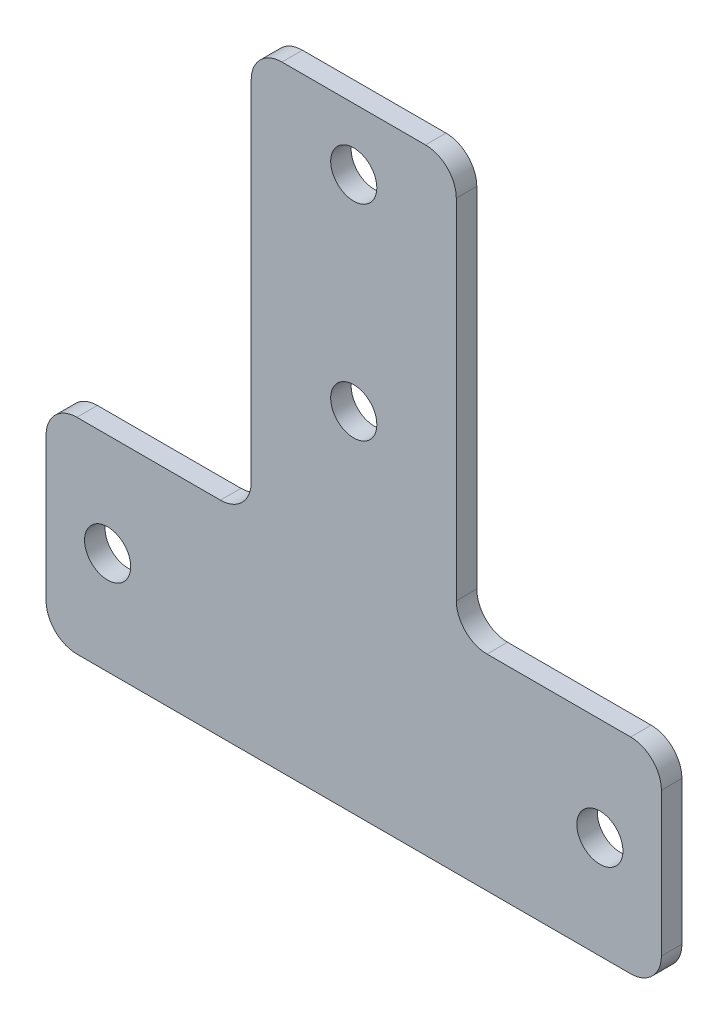
SolidWorks part; units mm, degrees
material "1023 碳钢板 (SS)"
ref_plane "前视基准面" through (0, 0, 0) normal (0, 0, 1) x (1, 0, 0)
ref_plane "上视基准面" through (0, 0, 0) normal (0, 1, 0) x (1, 0, 0)
ref_plane "右视基准面" through (0, 0, 0) normal (1, 0, 0) x (0, 0, -1)
sketch "草图1" plane through (0, 0, 0) normal (0, 0, 1) x (1, 0, 0)
  line L0 (0, 0) -> (37798.9194, 0) construction
  line L1 (0, 0) -> (0, 37798.9194) construction
  line L2 (-27, 0) -> (27, 0)
  line L3 (30, 3) -> (30, 17)
  line L4 (27, 20) -> (13, 20)
  line L5 (10, 23) -> (10, 32.5)
  line L6 (7, 60) -> (-7, 60)
  line L7 (-10, 57) -> (-10, 23)
  line L8 (-13, 20) -> (-27, 20)
  line L9 (-30, 17) -> (-30, 3)
  line L13 (10, 32.5) -> (10, 57)
  arc A0 (7, 60) -> (10, 57) centre (7, 57) cw
  arc A1 (13, 20) -> (10, 23) centre (13, 23) cw
  arc A2 (30, 17) -> (27, 20) centre (27, 17) ccw
  arc A3 (27, 0) -> (30, 3) centre (27, 3) ccw
  arc A4 (-27, 0) -> (-30, 3) centre (-27, 3) cw
  arc A5 (-27, 20) -> (-30, 17) centre (-27, 17) ccw
  arc A6 (-10, 23) -> (-13, 20) centre (-13, 23) cw
  arc A7 (-7, 60) -> (-10, 57) centre (-7, 57) ccw
  circle A8 centre (-24, 10) radius 2.25
  circle A9 centre (24, 10) radius 2.25
  circle A10 centre (0, 54) radius 2.25
  circle A11 centre (0, 34) radius 2.25
  point P15 (10, 60)
  point P22 (30, 0)
  point P25 (-30, 0)
  point P28 (-30, 20)
  point P33 (-10, 60)
  dimension "D5" = 3
  dimension "D6" = 4.5
  dimension "D8" = 10
  dimension "D10" = 20
  dimension "D12" = 3
  dimension "D9" = 6
  dimension "D1" = 20
  dimension "D2" = 20
  dimension "D3" = 60
  dimension "D4" = 60
  dimension "D7" = 24
base flange "基体-法兰1" sketch "草图1" thickness 2 reverse thickness direction no parameters "D1"=2
sketch "折弯-线1" plane through (0, 0, 0) normal (0, 1, 0) x (1, 0, 0)
sketch "边界框1" plane through (0, 0, 0) normal (0, 1, 0) x (1, 0, 0)
sheet metal parameters "钣金7" thickness 2 parameters "D1"=2
flat pattern "平板型式7" [suppressed]
sketch "折弯-线2" plane through (0, 0, 0) normal (0, 1, 0) x (1, 0, 0)
sketch "边界框2" [suppressed] plane through (0, 0, 0) normal (0, 1, 0) x (1, 0, 0)
